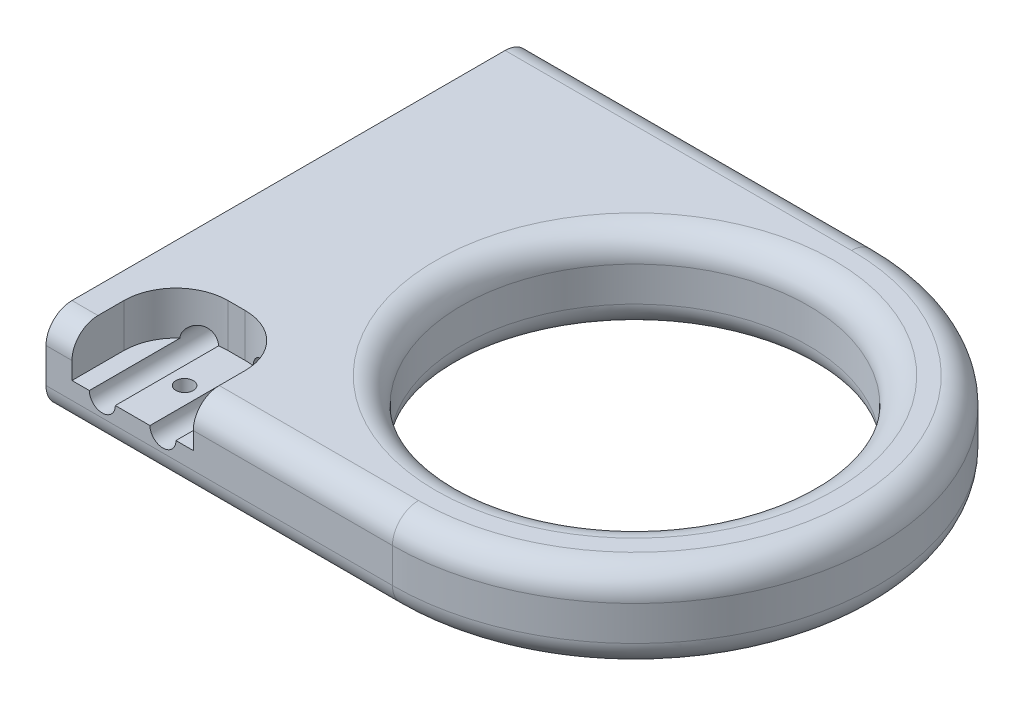
SolidWorks part; units mm, degrees
ref_plane "Front" through (0, 0, 0) normal (0, 0, 1) x (1, 0, 0)
ref_plane "Top" through (0, 0, 0) normal (0, 1, 0) x (1, 0, 0)
ref_plane "Right" through (0, 0, 0) normal (1, 0, 0) x (0, 0, -1)
other "Configuration Table"
sketch "Sketch1" plane through (0, 0, 0) normal (0, 1, 0) x (1, 0, 0)
  line L0 (0, -14) -> (-20, -14)
  line L1 (-20, -14) -> (-20, 14)
  line L2 (-20, 14) -> (0, 14)
  circle A0 centre (0, 0) radius 10
  arc A1 (0, -14) -> (0, 14) centre (0, 0) ccw
  point P3 (0, 0)
  dimension "D1" = 20
  dimension "D2" = 4
  dimension "D3" = 10
extrude "Boss-Extrude1" add sketch "Sketch1" along normal mid plane 5
ref_plane "Plane2" through (-10, 0, 0) normal (1, 0, 0) x (0, 0, -1)
sketch "Sketch3" plane through (0, 0, 14) normal (0, 0, 1) x (1, 0, 0)
  line L0 (-20, 2.5) -> (-20, -2.5) construction
  line L3 (-15, 5.1251) -> (-15, -10.2187) construction
  line L4 (-10, -2.75) -> (-10, 2.75) construction
  line L5 (-20, 2.5) -> (0, 2.5) construction
  line L6 (-18.5, 2.5) -> (-11.5, 2.5)
  line L7 (-18.5, 2.5) -> (-18.5, 0)
  line L8 (-18.5, 0) -> (-11.5, 0)
  line L9 (-11.5, 2.5) -> (-11.5, 0)
  circle A0 centre (-16.75, 0) radius 0.75
  circle A1 centre (-13.25, 0) radius 0.75
  point P13 (0, 0)
  line M6 (0, 2.5) -> (-20, 2.5)
  dimension "D2" = 1.5
  dimension "D1" = 1.5
  dimension "2" = 2
extrude "Cut-Extrude2" cut sketch "Sketch3" against normal through all contours L8 A0 | L8 A0 | L8 A1 | L8 A1 region at (-16.75, 0.3183, 14) region at (-16.75, -0.3183, 14) region at (-13.25, -0.3183, 14) region at (-13.25, 0.3183, 14)
extrude "Cut-Extrude3" cut sketch "Sketch3<3>" against normal blind 6 contours L3 L6 L7 L8 A0 | L3 L8 A1 L9 M6 region at (-13.25, 1.3546, 14) region at (-16.75, 1.3546, 14)
sketch "Sketch3<3>" plane through (0, 0, 14) normal (0, 0, 1) x (1, 0, 0) same geometry as "Sketch3"
sketch "Sketch7" plane through (0, 0, 0) normal (0, 1, 0) x (1, 0, 0)
  line L0 (-20.7943, -11) -> (-8.2045, -11) construction
  line L1 (-15, -5.5278) -> (-15, -15.3932) construction
  line L2 (-16, -8) -> (-16, -14) construction
  line L3 (-14, -8) -> (-14, -14) construction
  line L4 (-11.5, -8) -> (-18.5, -8) construction
  line L5 (-16, -14) -> (-14, -14) construction
  circle A0 centre (-15, -11) radius 0.5
  point P6 (0, 0)
  dimension "D1" = 1
extrude "Cut-Extrude5" cut sketch "Sketch7" against normal through all
fillet "Fillet1" radius 1.5 9 edges at (-10, -2.5, 14) (-10, -2.5, -14) (-5.75, 2.5, 14) (-10, 2.5, -14) (14, -2.5, 0) (14, 2.5, 0) (0, -2.5, 10) (0, 2.5, 10) (-19.25, 2.5, 14)
fillet "Fillet2" radius 3 2 edges at (-11.5, 1.25, 8) (-18.5, 1.25, 8)
